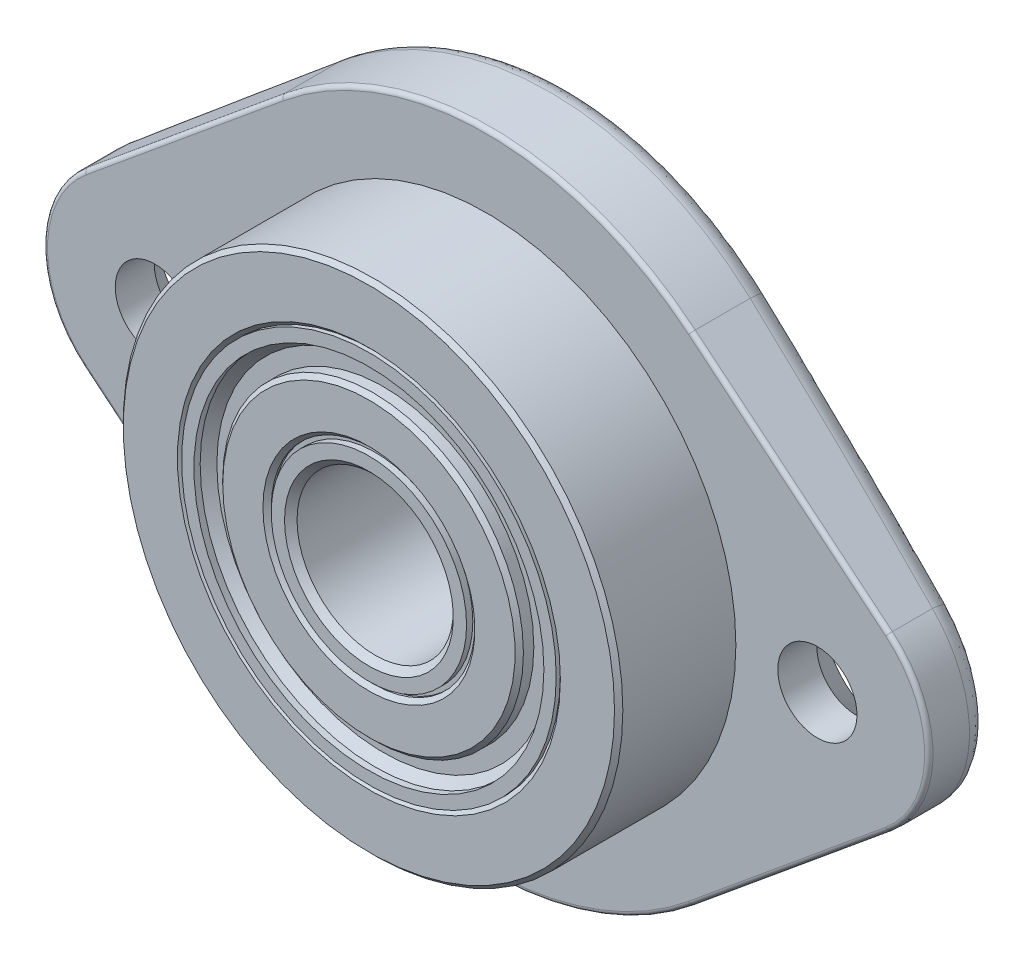
SolidWorks part; units mm, degrees
ref_plane "Front Plane" through (0, 0, 0) normal (0, 0, 1) x (1, 0, 0)
ref_plane "Top Plane" through (0, 0, 0) normal (0, 1, 0) x (1, 0, 0)
ref_plane "Right Plane" through (0, 0, 0) normal (1, 0, 0) x (0, 0, -1)
sketch "Sketch1" plane through (0, 0, 0) normal (0, 0, 1) x (1, 0, 0)
  line L0 (-26.9875, 0) -> (26.9875, 0) construction
  line L1 (0, 0) -> (0, 19.6453) construction
  line L2 (24.517, 5.241) -> (12.5023, 15.1536)
  line L3 (24.517, -5.241) -> (12.5023, -15.1536)
  line L4 (-20.193, 0) -> (20.193, 0) construction
  line L5 (-24.517, 5.241) -> (-12.5023, 15.1536)
  line L6 (-24.517, -5.241) -> (-12.5023, -15.1536)
  line L7 (-17.78, 0) -> (-15.2251, 0) construction
  circle A0 centre (0, 0) radius 4.7625
  circle A1 centre (-20.193, 0) radius 2.413
  circle A2 centre (20.193, 0) radius 2.413
  arc A3 (-24.517, 5.241) -> (-24.517, -5.241) centre (-20.193, 0) ccw
  arc A4 (24.517, 5.241) -> (24.517, -5.241) centre (20.193, 0) cw
  circle A5 centre (0, 0) radius 19.6453
  circle A6 centre (0, 0) radius 15.2251
  circle A7 centre (0, 0) radius 5.9531
  circle A8 centre (0, 0) radius 11.4188
  point P26 (0, 4.7625)
  point P27 (0, 11.4188)
  point P28 (0, 5.9531)
  dimension "D8" = 11.9063
  dimension "D10" = 22.8377
  dimension "D2" = 30.4502
sketch "Sketch3" plane through (0, 0, 0) normal (1, 0, 0) x (0, 0, -1)
  line L0 (-6.1516, 5.9531) -> (-5.7706, 5.9531)
  line L1 (-6.1516, 11.4188) -> (0.9922, 11.4188)
  line L2 (-6.1516, 11.4188) -> (-6.1516, 10.6677)
  line L3 (-6.1516, 4.7625) -> (0.9922, 4.7625)
  line L5 (-5.7706, 5.9531) -> (-5.7706, 6.2071)
  line L6 (-5.7706, 6.2071) -> (-6.1516, 6.2071)
  line L7 (-6.1516, 9.1655) -> (-5.2626, 9.1655)
  line L8 (-5.2626, 9.1655) -> (-5.2626, 10.6677)
  line L9 (-5.2626, 10.6677) -> (-6.1516, 10.6677)
  line L10 (-6.1516, 5.9531) -> (-6.1516, 4.7625)
  line L11 (-6.1516, 9.1655) -> (-6.1516, 6.2071)
  line L12 (0.9922, 11.4188) -> (0.9922, 4.7625)
  line L23 (-6.1516, 0) -> (6.1516, 0) construction
  point P14 (0.9922, 0)
  dimension "C" = 12.3031
  dimension "D1" = 0.254
  dimension "D2" = 0.381
  dimension "D3" = 6.6563
  dimension "D4" = 2.9584
  dimension "D5" = 0.889
  dimension "D6" = 2.2533
  dimension "D7" = 0.7511
  dimension "G" = 5.1594
revolve "Revolve1" add sketch "Sketch3" angle 360 about L23
chamfer "Chamfer2" distance 0.381 angle 45 1 edges at (4.7625, 0, 6.1516)
chamfer "Chamfer3" distance 0.254 angle 45 2 edges at (9.1655, 0, 6.1516) (6.2071, 0, 6.1516)
chamfer "Chamfer4" distance 0.508 angle 45 1 edges at (10.6677, 0, 5.2626)
sketch "Sketch2" plane through (0, 0, 0) normal (0, 0, 1) x (1, 0, 0)
  line L0 (24.517, 5.241) -> (12.5023, 15.1536) construction
  line L1 (24.517, -5.241) -> (12.5023, -15.1536) construction
  line L2 (-24.517, -5.241) -> (-12.5023, -15.1536) construction
  line L3 (-24.517, 5.241) -> (-12.5023, 15.1536) construction
  line L4 (24.517, 5.241) -> (12.5023, 15.1536)
  line L5 (24.517, -5.241) -> (12.5023, -15.1536)
  line L6 (-24.517, -5.241) -> (-12.5023, -15.1536)
  line L7 (-24.517, 5.241) -> (-12.5023, 15.1536)
  arc A0 (24.517, -5.241) -> (24.517, 5.241) centre (20.193, 0) ccw construction
  arc A1 (-24.517, 5.241) -> (-24.517, -5.241) centre (-20.193, 0) ccw construction
  circle A2 centre (0, 0) radius 19.6453 construction
  arc A3 (24.517, -5.241) -> (24.517, 5.241) centre (20.193, 0) ccw
  arc A4 (-24.517, 5.241) -> (-24.517, -5.241) centre (-20.193, 0) ccw
  arc A5 (12.5023, 15.1536) -> (-12.5023, 15.1536) centre (0, 0) ccw
  arc A6 (-12.5023, -15.1536) -> (12.5023, -15.1536) centre (0, 0) ccw
  circle A7 centre (20.193, 0) radius 2.413 construction
  circle A8 centre (-20.193, 0) radius 2.413 construction
  circle A9 centre (20.193, 0) radius 2.413
  circle A10 centre (-20.193, 0) radius 2.413
extrude "Extrude1" add sketch "Sketch2" along normal blind 5.1594 from vertex separate body starting at point (0, 0, -6.1516)
sketch "Sketch9" plane through (0, 0, -0.9922) normal (0, 0, 1) x (1, 0, 0)
  circle A0 centre (0, 0) radius 15.2251 construction
  circle A1 centre (0, 0) radius 11.4188 construction
  circle A2 centre (0, 0) radius 15.2251
  circle A3 centre (0, 0) radius 11.4188
extrude "Boss-Extrude2" add sketch "Sketch9" along normal up to vertex (7.1437 mm away) up to point (0, 0, 6.1516)
chamfer "Chamfer5" distance 0.254 angle 45 2 edges at (15.2251, 0, 6.1516) (11.4188, 0, 6.1516)
sketch "Sketch10" plane through (0, 0, -6.1516) normal (0, 0, -1) x (-1, 0, 0)
  circle A0 centre (-20.193, 0) radius 4.826
  circle A1 centre (20.193, 0) radius 4.826
  dimension "D1" = 9.652
extrude "Cut-Extrude2" cut sketch "Sketch10" against normal through all draft 41
sketch "Sketch5" plane through (0, 0, 0) normal (0, 1, 0) x (1, 0, 0)
  line L0 (12.5023, 6.1516) -> (-12.5023, 6.1516) construction
  line L2 (-26.9875, 4.6037) -> (-26.9875, 6.6596)
  line L3 (-26.9875, 6.6596) -> (26.9875, 6.6596)
  line L4 (26.9875, 4.6037) -> (26.9875, 6.6596)
  line L7 (-12.5023, 6.1516) -> (-24.517, 6.1516) construction
  line L8 (26.9875, 6.1516) -> (24.517, 6.1516) construction
  arc A0 (-26.9875, 4.6037) -> (26.9875, 4.6037) centre (0, -229.898) cw
  dimension "D1" = 1.5478
  dimension "D2" = 0.508
extrude "Cut-Extrude1" cut sketch "Sketch5" against normal through all both and the other way through all
fillet "Fillet2" radius 1.27 8 edges at (-18.5157, 10.1923, -5.4243) (0.307, 19.6429, -6.1514) (18.5157, 10.1923, -5.4243) (26.9305, 0.8783, -4.6103) (18.5157, -10.1923, -5.4243) (-0.307, -19.6429, -6.1514) (-18.5157, -10.1923, -5.4243) (-26.9305, -0.8783, -4.6103)
fillet "Fillet3" radius 0.254 8 edges at (18.5096, 10.1973, -0.9922) (26.9875, 0, -0.9922) (18.5096, -10.1973, -0.9922) (0, -19.6453, -0.9922) (-18.5096, -10.1973, -0.9922) (-26.9875, 0, -0.9922) (-18.5096, 10.1973, -0.9922) (0, 19.6453, -0.9922)
equation "\"D8@Sketch1\"=\"shaft dia@Sketch1\"*1.25"
equation "\"D4@Sketch3\"=\"D3@Sketch3\"/2.25"
equation "\"D1@Sketch5\" = \"G@Extrude1\"*.3"
equation "\"D7@Sketch3\"= \"D6@Sketch3\" / 3"
equation "\"D1@Sketch10\"=\"F@Sketch1\"*2"
equation "\"D2@Sketch1\"=\"D@Sketch1\"*.775"
equation "\"D10@Sketch1\"=\"D2@Sketch1\"*.75"
